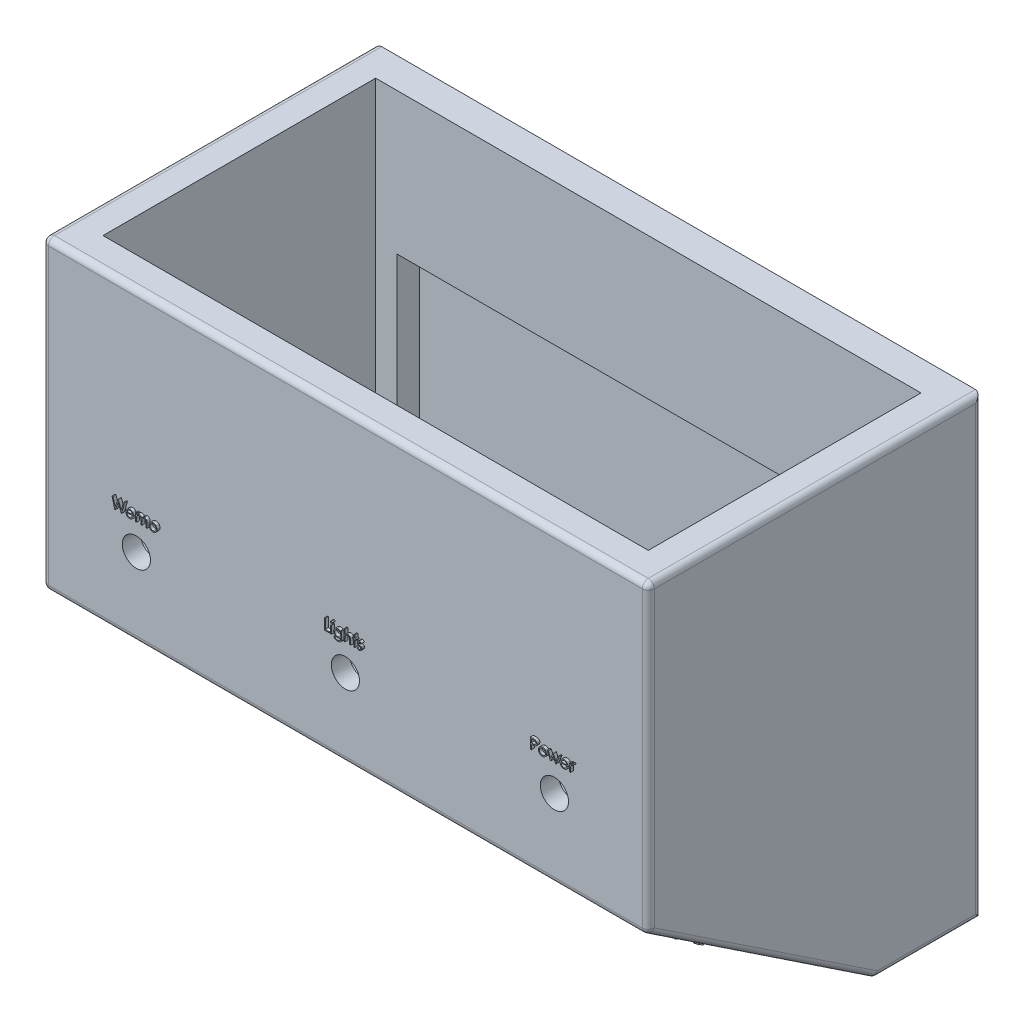
SolidWorks part; units mm, degrees
ref_plane "Front Plane" through (0, 0, 0) normal (0, 0, 1) x (1, 0, 0)
ref_plane "Top Plane" through (0, 0, 0) normal (0, 1, 0) x (1, 0, 0)
ref_plane "Right Plane" through (0, 0, 0) normal (1, 0, 0) x (0, 0, -1)
sketch "Sketch2" plane through (0, 0, 0) normal (0, 0, 1) x (1, 0, 0)
  line L1 (-100, 75) -> (100, 75)
  line L2 (-100, 75) -> (-100, -75)
  line L3 (-100, -75) -> (100, -75)
  line L4 (100, 75) -> (100, -75)
  line L5 (-100, 75) -> (100, -75) construction
  line L6 (-100, -75) -> (100, 75) construction
  point P0 (0, 0)
  dimension "D1" = 150
  dimension "D2" = 200
extrude "Boss-Extrude1" add sketch "Sketch2" along normal blind 35
sketch "Sketch3" plane through (0, 0, 35) normal (0, 0, 1) x (1, 0, 0)
  line L0 (100, -75) -> (100, 75) construction
  line L1 (-100, 75) -> (100, 75)
  line L2 (-100, 75) -> (-100, -25)
  line L3 (-100, -25) -> (100, -25)
  line L4 (100, 75) -> (100, -25)
  dimension "D1" = 100
extrude "Boss-Extrude2" add sketch "Sketch3" along normal blind 75
loft "Loft3" add section face at (0, -50, 35) section face at (0, -25, 72.5) connector at (-100, -75, 35) connector at (-100, -25, 110)
sketch "Sketch6" plane through (0, -68.0769, 45.3846) normal (0, -0.8321, 0.5547) x (1, 0, 0)
  line L1 (-33, 22.408) -> (13, 22.408)
  line L2 (-33, 22.408) -> (-33, 42.908)
  line L3 (-33, 42.908) -> (13, 42.908)
  line L4 (13, 22.408) -> (13, 42.908)
  line L5 (-33, 22.408) -> (13, 42.908) construction
  line L6 (-33, 42.908) -> (13, 22.408) construction
  line L7 (36, 18.658) -> (64, 18.658)
  line L8 (36, 18.658) -> (36, 46.658)
  line L9 (36, 46.658) -> (64, 46.658)
  line L10 (64, 18.658) -> (64, 46.658)
  line L11 (36, 18.658) -> (64, 46.658) construction
  line L12 (36, 46.658) -> (64, 18.658) construction
  line L13 (-100, 77.658) -> (100, 77.658) construction
  line L14 (-81.5, 9.7438) -> (-58.5, 9.7438)
  line L15 (-100, -12.4808) -> (-100, 77.658) construction
  line L16 (-81.5, 9.7438) -> (-81.5, 55.5722)
  line L17 (-81.5, 55.5722) -> (-58.5, 55.5722)
  line L18 (-58.5, 9.7438) -> (-58.5, 55.5722)
  line L19 (-81.5, 9.7438) -> (-58.5, 55.5722) construction
  line L20 (-81.5, 55.5722) -> (-58.5, 9.7438) construction
  line L21 (89.1768, 18.158) -> (73.7768, 18.158)
  line L22 (89.1768, 18.158) -> (89.1768, 46.658)
  line L23 (89.1768, 46.658) -> (73.7768, 46.658)
  line L24 (73.7768, 18.158) -> (73.7768, 46.658)
  line L25 (89.1768, 18.158) -> (73.7768, 46.658) construction
  line L26 (89.1768, 46.658) -> (73.7768, 18.158) construction
  line L27 (73.7768, 38.408) -> (89.1768, 38.408)
  line L28 (73.7768, 38.408) -> (73.7768, 26.408)
  line L29 (73.7768, 26.408) -> (89.1768, 26.408)
  line L30 (89.1768, 38.408) -> (89.1768, 26.408)
  line L31 (73.7768, 38.408) -> (89.1768, 26.408) construction
  line L32 (73.7768, 26.408) -> (89.1768, 38.408) construction
  line L33 (-31.75, 41.408) -> (11.75, 41.408)
  line L34 (-31.75, 41.408) -> (-31.75, 23.908)
  line L35 (-31.75, 23.908) -> (11.75, 23.908)
  line L36 (11.75, 41.408) -> (11.75, 23.908)
  line L37 (-31.75, 41.408) -> (11.75, 23.908) construction
  line L38 (-31.75, 23.908) -> (11.75, 41.408) construction
  line L39 (36, 39.066) -> (64, 39.066)
  line L40 (36, 39.066) -> (36, 18.658)
  line L41 (36, 18.658) -> (64, 18.658)
  line L42 (64, 39.066) -> (64, 18.658)
  line L43 (-15.5, 42.908) -> (-4.5, 42.908)
  line L44 (-15.5, 42.908) -> (-15.5, 41.408)
  line L45 (-15.5, 41.408) -> (-4.5, 41.408)
  line L46 (-4.5, 42.908) -> (-4.5, 41.408)
  circle A0 centre (-70, 32.658) radius 18.5
  circle A1 centre (-70, 32.658) radius 11.25
  point P2 (-10, 32.658)
  point P7 (50, 32.658)
  point P21 (81.4768, 32.408)
  point P22 (81.4768, 32.408)
  point P31 (-10, 32.658)
  dimension "D1" = 37
  dimension "D12" = 22.5
  dimension "D2" = 20.5
  dimension "D3" = 46
  dimension "D4" = 45
  dimension "D5" = 45
  dimension "D6" = 45
  dimension "D7" = 30
  dimension "D8" = 60
  dimension "D9" = 60
  dimension "D10" = 28
  dimension "D11" = 28
  dimension "D13" = 23
  dimension "D14" = 28.5
  dimension "D15" = 15.4
  dimension "D16" = 12
  dimension "D17" = 43.5
  dimension "D18" = 17.5
  dimension "D19" = 11
  dimension "D20" = 16.25
sketch "Sketch8" plane through (0, -68.0769, 45.3846) normal (0, -0.8321, 0.5547) x (1, 0, 0)
  line L1 (-100, 77.658) -> (100, 77.658)
  line L2 (-100, 77.658) -> (-100, -12.4808)
  line L3 (-100, -12.4808) -> (100, -12.4808)
  line L4 (100, 77.658) -> (100, -12.4808)
sketch "Sketch9" plane through (0, 75, 0) normal (0, 1, 0) x (1, 0, 0)
  line L1 (-100, 0) -> (100, 0)
  line L2 (-100, 0) -> (-100, -110)
  line L3 (-100, -110) -> (100, -110)
  line L4 (100, 0) -> (100, -110)
shell "Shell2" thickness 10 removed face at (0, 75, 55)
sketch "Sketch26" plane through (0, -75, 0) normal (0, -1, 0) x (1, 0, 0)
  line L0 (0, 0) -> (0, 35) construction
  line L1 (-100, 35) -> (100, 35) construction
  line L3 (14.25, 2) -> (-14.25, 2)
  line L4 (14.25, 2) -> (14.25, 33)
  line L5 (14.25, 33) -> (-14.25, 33)
  line L6 (-14.25, 2) -> (-14.25, 33)
  line L7 (14.25, 2) -> (-14.25, 33) construction
  line L8 (14.25, 33) -> (-14.25, 2) construction
  point P5 (0, 17.5)
  dimension "D1" = 31
  dimension "D2" = 28.5
extrude "Cut-Extrude12" cut sketch "Sketch26" against normal blind 15
sketch "Sketch28" plane through (0, -75, 0) normal (0, -1, 0) x (1, 0, 0)
  line L0 (14.25, 2) -> (14.25, 33) construction
  line L1 (14.25, 33) -> (-14.25, 33) construction
  ellipse E0 centre (14.25, 17.25) end of major axis (6.15, 17.25) minor radius 7
  ellipse E1 centre (-14.25, 17.25) end of major axis (-22.35, 17.25) minor radius 7
  dimension "D1" = 7
  dimension "D2" = 8.75
  dimension "D3" = 8.1
  dimension "D4" = 2
extrude "Cut-Extrude13" cut sketch "Sketch28" against normal blind 9
sketch "Sketch29" plane through (0, -60, 0) normal (0, -1, 0) x (1, 0, 0)
  line L0 (-14.25, 10) -> (14.25, 10) construction
  circle A0 centre (0, 10) radius 5
  dimension "D1" = 10
extrude "Cut-Extrude14" cut sketch "Sketch29" against normal blind 7.5
fillet "Fillet1" radius 2 2 edges at (0, -52.5, 10) (0, -60, 5)
fillet "Fillet2" radius 2 12 edges at (100, -75, 17.5) (100, -50, 72.5) (100, 75, 55) (100, 0, 0) (-100, 0, 0) (-100, 75, 55) (-100, -50, 72.5) (-100, -75, 17.5) (0, 75, 110) (100, 25, 110) (0, -25, 110) (-100, 25, 110)
fillet "Fillet3" radius 2 3 edges at (-99.4142, -74.4142, 34.8226) (99.4142, -74.4142, 34.8226) (0, -75, 35)
sketch "Sketch30" plane through (0, -66, 0) normal (0, -1, 0) x (1, 0, 0)
  line L0 (14.25, 17.25) -> (22.35, 17.25) construction
  line L1 (14.25, 24.25) -> (14.25, 10.25) construction
  line L2 (14.25, 10.25) -> (14.25, 24.25) construction
  line L7 (22.35, 17.25) -> (-22.35, 17.25) construction
  line L8 (0, 17.25) -> (0, 25.5372) construction
  line L9 (-19.35, 17.25) -> (-19.35, 20.6868) construction
  circle A0 centre (19.35, 17.25) radius 1.05
  circle A1 centre (-19.35, 17.25) radius 1.05
  ellipse E0 centre (14.25, 17.25) end of major axis (6.15, 17.25) minor radius 7 (14.25, 10.25) -> (14.25, 24.25) ccw construction
  ellipse E1 centre (14.25, 17.25) end of major axis (6.15, 17.25) minor radius 7 (14.25, 10.25) -> (14.25, 24.25) ccw construction
  ellipse E2 centre (-14.25, 17.25) end of major axis (-22.35, 17.25) minor radius 7 (-14.25, 24.25) -> (-14.25, 10.25) ccw construction
  dimension "D1" = 2.1
  dimension "D2" = 3
  dimension "D3" = 3
  dimension "D4" = 2
extrude "Cut-Extrude16" cut sketch "Sketch30" against normal blind 10
sketch "Sketch34" plane through (0, 0, 110) normal (0, 0, 1) x (1, 0, 0)
  line L0 (0, 0) -> (-98, 0) construction
  line L1 (-98, 73) -> (-98, -23.9296) construction
  line L2 (0, 0) -> (0, 73) construction
  line L3 (98, 73) -> (-98, 73) construction
  circle A0 centre (-69, 0) radius 4.65
  circle A1 centre (-69, 0) radius 3.5
  circle A2 centre (0, 0) radius 4.65
  circle A3 centre (0, 0) radius 3.5
  circle A4 centre (69, 0) radius 4.65
  circle A5 centre (69, 0) radius 3.5
  dimension "D1" = 9.3
  dimension "D2" = 7
  dimension "D3" = 29
  dimension "D4" = 3
extrude "Cut-Extrude18" cut sketch "Sketch34" against normal blind 15 contours A3 | A5 | A1
extrude "Cut-Extrude19" cut sketch "Sketch34<3>" against normal blind 6
sketch "Sketch34<3>" plane through (0, 0, 110) normal (0, 0, 1) x (1, 0, 0) same geometry as "Sketch34"
fillet "Fillet4" radius 2 3 edges at (-65.5, 0, 104) (3.5, 0, 104) (72.5, 0, 104)
sketch "Sketch35" plane through (0, 0, 10) normal (0, 0, 1) x (1, 0, 0)
  line L1 (83, -28.25) -> (-83, -28.25)
  line L2 (83, -28.25) -> (83, 28.25)
  line L3 (83, 28.25) -> (-83, 28.25)
  line L4 (-83, -28.25) -> (-83, 28.25)
  line L5 (83, -28.25) -> (-83, 28.25) construction
  line L6 (83, 28.25) -> (-83, -28.25) construction
  point P0 (0, 0)
  dimension "D1" = 56.5
  dimension "D2" = 166
extrude "Cut-Extrude20" cut sketch "Sketch35" against normal blind 7.5
sketch "Sketch38" plane through (0, -68.0769, 45.3846) normal (0, -0.8321, 0.5547) x (1, 0, 0)
  text T0 "           Volume/\r\nChange Playlist" font "Century Gothic" height 3.5
extrude "Boss-Extrude8" add sketch "Sketch38" along normal blind 1
sketch "Sketch39" plane through (0, 0, 110) normal (0, 0, 1) x (1, 0, 0)
  line L0 (0, 0) -> (0, 9.7465) construction
  line L1 (0, 9.7465) -> (75.4341, 9.7465) construction
  line L2 (75.4341, 9.7465) -> (-74.7186, 9.7465) construction
sketch "Sketch42" plane through (0, 0, 2.5) normal (0, 0, 1) x (1, 0, 0)
  line L0 (69.0994, 0) -> (69.0994, 9.7465) construction
  line L1 (-69.0387, 0) -> (-69.0387, 17.9151) construction
  line L2 (0, 9.7465) -> (75.4341, 9.7465) construction
  text T0 "Power"
  text T1 "Lights"
  text T2 "Wemo"
  point P2 (0, 0)
  point P5 (0, 0)
  point P6 (69.0994, 9.7465)
extrude "Boss-Extrude10" add sketch "Sketch42" along normal blind 1 from surface starting at face at (-64.35, 0, 110)
extrude "Cut-Extrude23" cut sketch "Sketch6" against normal blind 15 contours L36 L33 L34 L35 | L18 A0 | L16 A0 | L8 L39 L10 L9 | L29 L24 L21 L22 | L24 L27 L22 L23 region at (-10, -49.9615, 72.5577) region at (50, -44.3013, 81.048) region at (-84.351, -49.9615, 72.5577) region at (-55.649, -49.9615, 72.5577) region at (81.4768, -55.7165, 63.9252) region at (81.4768, -44.4838, 80.7742)
ref_plane "Plane7" through (-31.75, -54.8151, 65.2773) normal (1, 0, 0) x (0, 0, -1)
extrude "Cut-Extrude25" cut sketch "Sketch6<6>" against normal blind 8 contours L1 L4 L3 L2 L33 L36 L35 L34 region at (-32.4964, -49.9615, 72.5577)
sketch "Sketch6<6>" plane through (0, -68.0769, 45.3846) normal (0, -0.8321, 0.5547) x (1, 0, 0) same geometry as "Sketch6"
extrude "Cut-Extrude26" cut sketch "Sketch6<7>" against normal blind 5 contours L18 A0 L16 A1 region at (-81.4564, -49.9615, 72.5577)
sketch "Sketch6<7>" plane through (0, -68.0769, 45.3846) normal (0, -0.8321, 0.5547) x (1, 0, 0) same geometry as "Sketch6"
extrude "Cut-Extrude27" cut sketch "Sketch6<8>" against normal blind 7 contours L39 L8 L7 L10 region at (50, -52.0671, 69.3993)
sketch "Sketch6<8>" plane through (0, -68.0769, 45.3846) normal (0, -0.8321, 0.5547) x (1, 0, 0) same geometry as "Sketch6"
extrude "Cut-Extrude28" cut sketch "Sketch6<9>" against normal blind 7 contours L24 L29 L22 L27 region at (81.4768, -50.1002, 72.3497)
sketch "Sketch6<9>" plane through (0, -68.0769, 45.3846) normal (0, -0.8321, 0.5547) x (1, 0, 0) same geometry as "Sketch6"
extrude "Cut-Extrude29" cut sketch "Sketch6<10>" against normal blind 15 contours L46 L3 L44 L33 region at (-10, -44.6919, 80.4622)
sketch "Sketch6<10>" plane through (0, -68.0769, 45.3846) normal (0, -0.8321, 0.5547) x (1, 0, 0) same geometry as "Sketch6"
sketch "Sketch5" plane through (0, -72.7941, 121.3235) normal (0, -0.5145, 0.8575) x (1, 0, 0)
  line L1 (-250, 55.737) -> (250, 55.737)
  line L2 (-250, 55.737) -> (-250, -90.0368)
  line L3 (-250, -90.0368) -> (250, -90.0368)
  line L4 (250, 55.737) -> (250, -90.0368)
  line L5 (136, -14.25) -> (164, -14.25)
  line L6 (136, -14.25) -> (136, 14.25)
  line L7 (136, 14.25) -> (164, 14.25)
  line L8 (164, -14.25) -> (164, 14.25)
  line L9 (136, -14.25) -> (164, 14.25) construction
  line L10 (136, 14.25) -> (164, -14.25) construction
  line L11 (23, -10.5) -> (-23, -10.5)
  line L12 (23, -10.5) -> (23, 10.5)
  line L13 (23, 10.5) -> (-23, 10.5)
  line L14 (-23, -10.5) -> (-23, 10.5)
  line L15 (23, -10.5) -> (-23, 10.5) construction
  line L16 (23, 10.5) -> (-23, -10.5) construction
  circle A0 centre (-150, 0) radius 18.5
  point P8 (150, 0)
  point P9 (-250, -17.1499)
  point P16 (0, 0)
  dimension "D1" = 37
  dimension "D2" = 100
  dimension "D4" = 28
  dimension "D5" = 28.5
  dimension "D6" = 100
  dimension "D7" = 21
  dimension "D8" = 46
